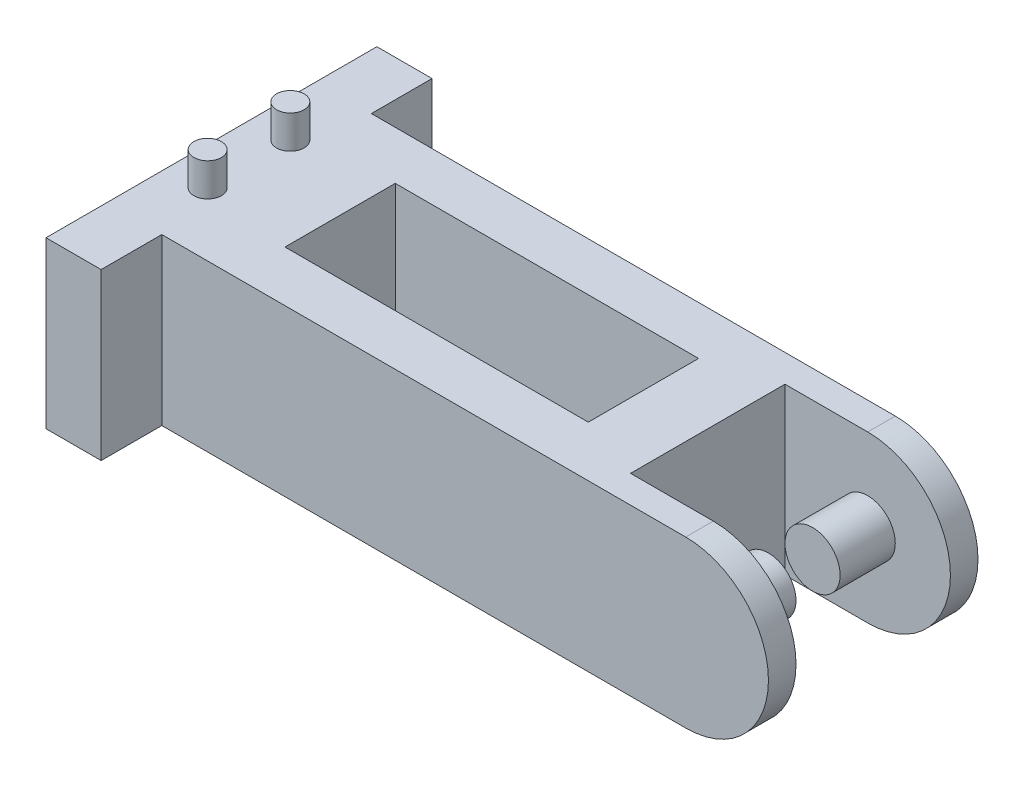
SolidWorks part; units mm, degrees
ref_plane "Front Plane" through (0, 0, 0) normal (0, 0, 1) x (1, 0, 0)
ref_plane "Top Plane" through (0, 0, 0) normal (0, 1, 0) x (1, 0, 0)
ref_plane "Right Plane" through (0, 0, 0) normal (1, 0, 0) x (0, 0, -1)
sketch "Sketch1" plane through (0, 0, 0) normal (0, 1, 0) x (1, 0, 0)
  line L0 (-91.6492, 0) -> (88.3826, 0) construction
  line L2 (-13.125, 30) -> (-13.125, 19)
  line L3 (-13.125, 19) -> (96.875, 19)
  line L4 (96.875, 19) -> (96.875, 14)
  line L5 (96.875, 14) -> (66.875, 14)
  line L6 (66.875, 14) -> (66.875, -14)
  line L9 (-23.125, 30) -> (-23.125, -30)
  line L12 (96.875, -14) -> (66.875, -14)
  line L13 (96.875, -19) -> (96.875, -14)
  line L14 (-13.125, -19) -> (96.875, -19)
  line L15 (-13.125, -30) -> (-13.125, -19)
  line L17 (-23.125, 30) -> (-13.125, 30)
  line L18 (-23.125, -30) -> (-13.125, -30)
  point P14 (-23.125, 0)
  point P17 (66.875, 0)
  dimension "D1" = 14
  dimension "D2" = 5
  dimension "D3" = 30
  dimension "D4" = 110
  dimension "D5" = 30
  dimension "D6" = 60
  dimension "D8" = 120
extrude "Boss-Extrude1" add sketch "Sketch1" along normal blind 15 and the other way blind 15
sketch "Sketch4" plane through (0, 0, 19) normal (0, 0, 1) x (1, 0, 0)
  line L0 (81.875, 15) -> (96.875, 15)
  line L1 (-13.125, 15) -> (96.875, 15) construction
  line L2 (-13.125, -15) -> (96.875, -15) construction
  line L4 (96.875, 15) -> (96.875, -15)
  line L5 (96.875, -15) -> (81.875, -15)
  arc A0 (81.875, -15) -> (81.875, 15) centre (81.875, 0) ccw
  line M5 (96.875, -15) -> (96.875, 15)
  line M6 (96.875, 15) -> (-13.125, 15)
  line M8 (-13.125, -15) -> (96.875, -15)
extrude "Cut-Extrude1" cut sketch "Sketch4" against normal blind 38 contours A0 L4 M6 | A0 M8 M5 region at (93.5245, -11.6495, 19) region at (93.5245, 11.6495, 19)
sketch "Sketch6" plane through (0, 15, 0) normal (0, 1, 0) x (1, 0, 0)
  line L1 (0, 10.206) -> (55, 10.206)
  line L2 (0, 10.206) -> (0, -9.794)
  line L3 (0, -9.794) -> (55, -9.794)
  line L4 (55, 10.206) -> (55, -9.794)
  dimension "D1" = 20
  dimension "D2" = 55
extrude "Cut-Extrude2" cut sketch "Sketch6" against normal blind 38
sketch "Sketch8" plane through (0, 0, 14) normal (0, 0, -1) x (-1, 0, 0)
  circle A0 centre (-81.875, 0) radius 5
  arc A1 (-81.875, 15) -> (-81.875, -15) centre (-81.875, 0) ccw construction
  dimension "D1" = 10
extrude "Boss-Extrude2" add sketch "Sketch8" along normal blind 10
ref_plane "Plane1" through (0, 0, 0) normal (0, 0, 1) x (1, 0, 0)
mirror "Mirror1" about plane through (0, 0, 0) normal (0, 0, 1) of "Boss-Extrude2"
sketch "Sketch9" plane through (0, 15, 0) normal (0, 1, 0) x (1, 0, 0)
  line L0 (-39.8643, 0) -> (4.2798, 0) construction
  line L1 (-16.5, 0) -> (16.5, 0) construction
  circle A0 centre (-16.3208, 7.5) radius 2.5
  circle A1 centre (-16.3208, -7.5) radius 2.5
  point P9 (0, 0)
  point P10 (0, 0)
  dimension "D1" = 5
  dimension "D2" = 15
  dimension "D3" = 7.5
extrude "Boss-Extrude3" add sketch "Sketch9" along normal blind 6
